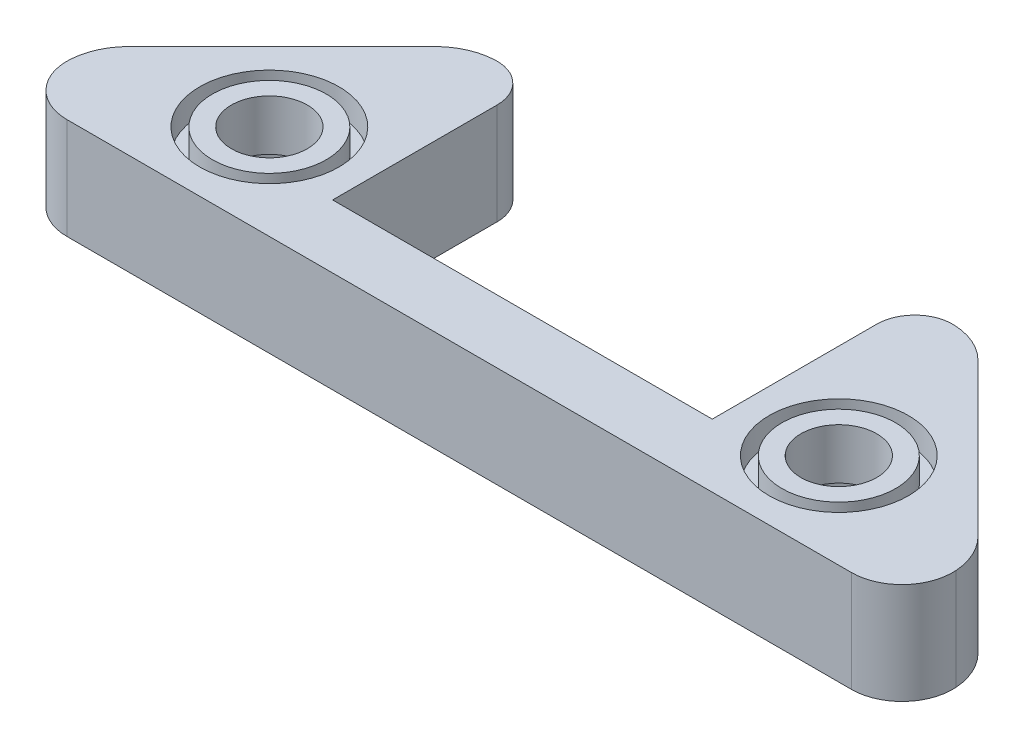
SolidWorks part; units mm, degrees
ref_plane "Plan de face" through (0, 0, 0) normal (0, 0, 1) x (1, 0, 0)
ref_plane "Plan de dessus" through (0, 0, 0) normal (0, 1, 0) x (1, 0, 0)
ref_plane "Plan de droite" through (0, 0, 0) normal (1, 0, 0) x (0, 0, -1)
sketch "Esquisse1" plane through (0, 0, 0) normal (0, 1, 0) x (1, 0, 0)
  line L0 (30, 0) -> (15, 15) construction
  line L1 (15, 0) -> (30, 0) construction
  line L2 (15, 15) -> (30, 15) construction
  line L3 (30, 0) -> (30, 15) construction
  line L4 (-15, 0) -> (-30, 0) construction
  line L5 (-15, 0) -> (-15, 15) construction
  line L6 (-15, 15) -> (-30, 15) construction
  line L7 (-30, 0) -> (-30, 15) construction
  line L8 (-15, 15) -> (-30, 0) construction
  line L9 (-15, 0) -> (15, 0) construction
  line L10 (-35, 0) -> (35, 0)
  line L13 (-15, 0) -> (-15, 5) construction
  line L16 (15, 0) -> (15, 5) construction
  line L17 (15, 15) -> (15, 5) construction
  line L18 (15, 5) -> (15, 21)
  line L21 (-15, 21) -> (-15, 5)
  line L22 (-15, 5) -> (15, 5)
  line L23 (-15, 21) -> (-20, 21)
  line L24 (-20, 21) -> (-35, 6)
  line L25 (-35, 6) -> (-35, 0)
  line L26 (15, 21) -> (20, 21)
  line L27 (20, 21) -> (35, 6)
  line L28 (35, 6) -> (35, 0)
  circle A0 centre (22.5, 7.5) radius 3
  circle A1 centre (-22.5, 7.5) radius 3
  circle A2 centre (22.5, 7.5) radius 7.5 construction
  point P17 (0, 0)
  point P26 (0, 0)
  dimension "D1" = 6
  dimension "D2" = 30
  dimension "D3" = 15
  dimension "D4" = 5
  dimension "D5" = 16
  dimension "D6" = 20
  dimension "D7" = 5
  dimension "D8" = 6
extrude "Boss.-Extru.1" add sketch "Esquisse1" along normal blind 8
sketch "Esquisse3" plane through (0, 8, 0) normal (0, 1, 0) x (1, 0, 0)
  circle A0 centre (-22.5, 7.5) radius 5.5
  circle A1 centre (22.5, 7.5) radius 5.5
  circle A2 centre (-22.5, 7.5) radius 4.5
  circle A3 centre (22.5, 7.5) radius 4.5
  point P9 (22.5, 7.5)
  dimension "D1" = 11
  dimension "D2" = 9
extrude "Enlèv. mat.-Extru.2" cut sketch "Esquisse3" against normal blind 2
sketch "Esquisse4" plane through (0, 0, 0) normal (0, -1, 0) x (1, 0, 0)
  circle A0 centre (-22.5, -7.5) radius 6.1
  circle A1 centre (22.5, -7.5) radius 6.1
  dimension "D1" = 12.2
  dimension "D2" = 12.2
extrude "Enlèv. mat.-Extru.3" cut sketch "Esquisse4" against normal offset from surface (4 mm away) 2 up to face at (-22.5, 6, -3)
fillet "Congé1" radius 5 4 edges at (35, 4, -6) (20, 4, -21) (-20, 4, -21) (-35, 4, -6)
fillet "Congé2" radius 3 2 edges at (15, 4, -21) (-15, 4, -21)
fillet "Congé3" radius 4 2 edges at (35, 4, 0) (-35, 4, 0)
